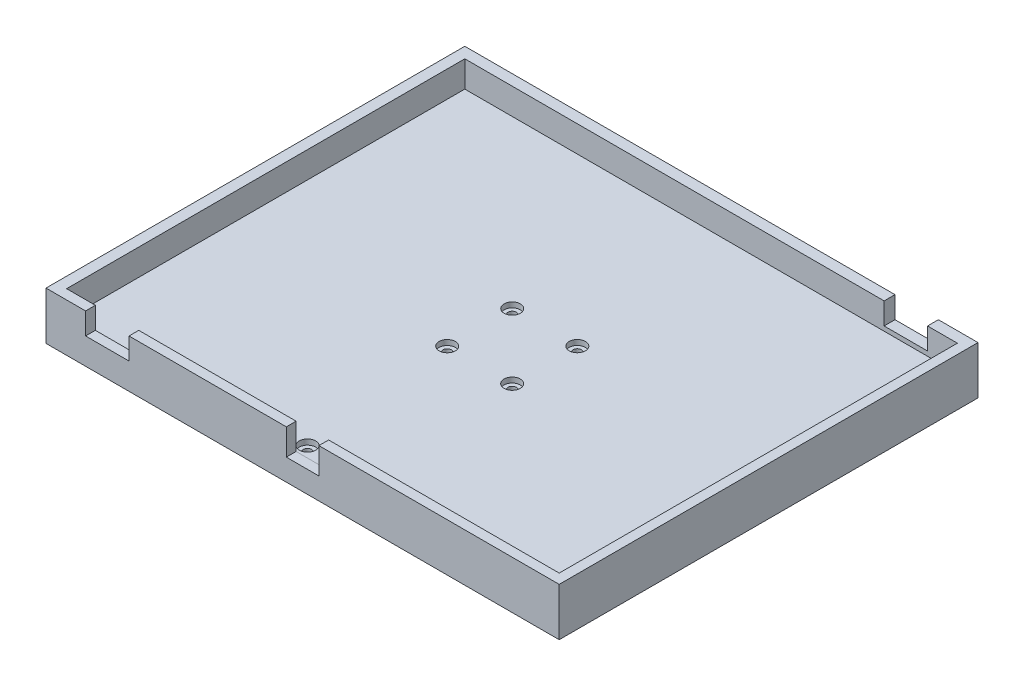
SolidWorks part; units mm, degrees
note: The reader was unsure of these and kept them because the rebuilt part matched: shared geometry of "Sketch44<4>", "Sketch47<2>".
ref_plane "Front Plane" through (0, 0, 0) normal (0, 0, 1) x (1, 0, 0)
ref_plane "Top Plane" through (0, 0, 0) normal (0, 1, 0) x (1, 0, 0)
ref_plane "Right Plane" through (0, 0, 0) normal (1, 0, 0) x (0, 0, -1)
sketch "Sketch2" plane through (0, 0, 0) normal (0, 1, 0) x (1, 0, 0)
  line L1 (0, 0) -> (227, 0)
  line L2 (0, 0) -> (0, -183.5)
  line L3 (0, -183.5) -> (227, -183.5)
  line L4 (227, 0) -> (227, -183.5)
  line L5 (-5, 5) -> (231.5, 5)
  line L6 (-5, 5) -> (-5, -188)
  line L7 (-5, -188) -> (231.5, -188)
  line L8 (231.5, 5) -> (231.5, -188)
  dimension "D1" = 227
  dimension "D2" = 183.5
  dimension "D3" = 236.5
  dimension "D4" = 5
  dimension "D5" = 193
  dimension "D6" = 5
extrude "Boss-Extrude1" add sketch "Sketch2" along normal blind 12.1
sketch "Sketch3" plane through (0, 0, 0) normal (0, -1, 0) x (1, 0, 0)
  line L1 (-5, 188) -> (231.5, 188)
  line L2 (-5, 188) -> (-5, -5)
  line L3 (-5, -5) -> (231.5, -5)
  line L4 (231.5, 188) -> (231.5, -5)
extrude "Boss-Extrude2" add sketch "Sketch3" along normal blind 10
sketch "Sketch4" plane through (-5, 0, 0) normal (-1, 0, 0) x (0, 0, 1)
  line L0 (-5, 12.1) -> (188, 12.1) construction
  line L1 (81.5, 12.1) -> (101.5, 12.1)
  line L2 (81.5, 12.1) -> (81.5, 2.1)
  line L3 (81.5, 2.1) -> (101.5, 2.1)
  line L4 (101.5, 12.1) -> (101.5, 2.1)
  line L5 (91.5, -10) -> (91.5, 12.1)
  line L6 (188, -10) -> (-5, -10) construction
  line M4 (188, 12.1) -> (-5, 12.1)
  dimension "D1" = 10
  dimension "D2" = 20
  dimension "D3" = 10
extrude "Cut-Extrude1" cut sketch "Sketch4" against normal blind 5 contours L5 L3 L4 M4 | L3 L5 L1 L2
sketch "Sketch7" plane through (0, 0, 188) normal (0, 0, 1) x (1, 0, 0)
  line L0 (113.25, 12.1) -> (113.25, -10) construction
  line L1 (-5, 12.1) -> (231.5, 12.1) construction
  line L2 (231.5, -10) -> (-5, -10) construction
  line L4 (13.25, 12.1) -> (33.25, 12.1)
  line L5 (13.25, 12.1) -> (13.25, 2.1)
  line L6 (13.25, 2.1) -> (33.25, 2.1)
  line L7 (33.25, 12.1) -> (33.25, 2.1)
  dimension "D1" = 20
  dimension "D2" = 100
  dimension "D3" = 10
extrude "Cut-Extrude2" cut sketch "Sketch7" against normal blind 5
sketch "Sketch8" plane through (0, 0, -5) normal (0, 0, -1) x (-1, 0, 0)
  line L0 (-113.25, 12.1) -> (-113.25, -10) construction
  line L1 (-231.5, 12.1) -> (5, 12.1) construction
  line L2 (5, -10) -> (-231.5, -10) construction
  line L4 (-213.25, 12.1) -> (-193.25, 12.1)
  line L5 (-213.25, 12.1) -> (-213.25, 2.1)
  line L6 (-213.25, 2.1) -> (-193.25, 2.1)
  line L7 (-193.25, 12.1) -> (-193.25, 2.1)
  dimension "D1" = 10
  dimension "20" = 20
  dimension "D2" = 200
extrude "Cut-Extrude3" cut sketch "Sketch8" against normal blind 5
sketch "Sketch11" plane through (0, 0, -5) normal (0, 0, -1) x (-1, 0, 0)
  line L0 (-202.0531, 2.1) -> (-202.0531, -10)
  line L1 (-213.25, 2.1) -> (-193.25, 2.1) construction
  line L2 (5, -10) -> (-231.5, -10) construction
sketch "Sketch21" plane through (0, -10, 0) normal (0, -1, 0) x (1, 0, 0)
  circle A1 centre (128.25, 106.5) radius 1.925
  circle A4 centre (128.25, 76.5) radius 1.925
  circle A5 centre (98.25, 76.5) radius 1.925
  circle A6 centre (98.25, 106.5) radius 1.925
  point P4 (124.8714, 82.0162)
sketch "Sketch32" plane through (0, 0, 0) normal (1, 0, 0) x (0, 0, -1)
  line L0 (0, 0) -> (-183.5, 0) construction
  line L1 (-101.5, 12.1) -> (-81.5, 12.1)
  line L2 (-101.5, 12.1) -> (-101.5, 0)
  line L3 (-101.5, 0) -> (-81.5, 0)
  line L4 (-81.5, 12.1) -> (-81.5, 0)
extrude "Cut-Extrude14" cut sketch "Sketch32" against normal through all
sketch "Sketch34" plane through (0, 0, 0) normal (0, 1, 0) x (1, 0, 0)
  line L0 (113.3485, -91.6275) -> (113.5, -91.75)
  line L3 (113.6511, -91.6279) -> (113.5, -91.75)
  line L5 (-5, -91.5) -> (227, -91.75)
  line L6 (-5, -101.5) -> (-5, -81.5) construction
  line L7 (227, -183.5) -> (227, 0) construction
  line L8 (113.5, 0) -> (113.5, -183.5)
  line L9 (227, 0) -> (0, 0) construction
  line L10 (0, -183.5) -> (227, -183.5) construction
  circle A0 centre (128.5, -76.6438) radius 1.925
  circle A1 centre (128.4677, -106.6438) radius 1.925
  circle A2 centre (98.5323, -106.6438) radius 1.925
  circle A3 centre (98.5, -76.6438) radius 1.925
  dimension "D1" = 3.85
  dimension "D2" = 15
  dimension "D3" = 15
extrude "Cut-Extrude16" cut sketch "Sketch34" against normal through all contours A0 | A3 | A2 | A1
sketch "Sketch35" plane through (0, 0, 0) normal (0, 1, 0) x (1, 0, 0)
  line L0 (227, -91.75) -> (-5, -91.5)
  line L1 (227, -183.5) -> (227, 0) construction
  line L2 (-5, -101.5) -> (-5, -81.5) construction
  line L3 (113.5, 0) -> (113.5, -183.5)
  line L4 (227, 0) -> (0, 0) construction
  line L5 (0, -183.5) -> (227, -183.5) construction
  circle A0 centre (128.5, -76.6438) radius 3.75
  circle A1 centre (128.4677, -106.6438) radius 3.75
  circle A2 centre (98.5323, -106.6438) radius 3.75
  circle A3 centre (98.5, -76.6438) radius 3.75
  circle M5 centre (98.5323, -106.6438) radius 1.925
  circle M6 centre (128.5, -76.6438) radius 1.925
  circle M15 centre (98.5, -76.6438) radius 1.925
  dimension "D1" = 7.5
extrude "Cut-Extrude17" cut sketch "Sketch35" against normal blind 2.4 contours A3 M15 | A0 M6 | A2 M5 | A1
sketch "Sketch36" plane through (0, 0, 0) normal (1, 0, 0) x (0, 0, -1)
  line L0 (-81.5, 12.1) -> (-81.5, 0) construction
  line L1 (-101.5, 12.1) -> (-81.5, 12.1)
  line L2 (-101.5, 12.1) -> (-101.5, 0)
  line L3 (-101.5, 0) -> (-81.5, 0)
  line L4 (-81.5, 12.1) -> (-81.5, 0)
extrude "Boss-Extrude9" add sketch "Sketch36" along direction (1, 0, 0) on the side against the normal up to vertex (5 mm away)
sketch "Sketch37" plane through (0, 0, 188) normal (0, 0, 1) x (1, 0, 0)
  line L0 (113.25, -10) -> (113.25, 12.1)
  line L1 (231.5, -10) -> (-5, -10) construction
  line L2 (33.25, 12.1) -> (231.5, 12.1) construction
  line L4 (105.75, 12.1001) -> (120.75, 12.1001)
  line L5 (105.75, 12.1001) -> (105.75, 0.0001)
  line L6 (105.75, 0.0001) -> (120.75, 0.0001)
  line L7 (120.75, 12.1001) -> (120.75, 0.0001)
  line M11 (231.5, 12.1) -> (33.25, 12.1)
  dimension "D1" = 12.1
  dimension "D2" = 15
  dimension "0" = 0.0001
  dimension "D3" = 7.5
extrude "Cut-Extrude18" cut sketch "Sketch37" against normal blind 5 contours L5 L6 L0 M11 | L7 L0 L6 M11
sketch "Sketch41" plane through (0, 0, 0) normal (0, 1, 0) x (1, 0, 0)
  line L0 (113.5, 0) -> (113.5, -147.1209)
  line L1 (227, 0) -> (0, 0) construction
  line L2 (227, -91.75) -> (45.6317, -91.75)
  line L3 (227, -183.5) -> (227, 0) construction
  circle A0 centre (128.5, -76.6438) radius 1.925 construction
  circle A2 centre (128.5, -76.6438) radius 3.75 construction
  dimension "D2" = 15.1062
  dimension "D3" = 15.1062
  dimension "D1" = 15
sketch "Sketch44" plane through (0, 0, 0) normal (0, 1, 0) x (1, 0, 0)
  line L0 (113.5, 0) -> (113.5, -183.5) construction
  line L1 (227, 0) -> (0, 0) construction
  line L2 (0, -183.5) -> (227, -183.5) construction
  line L3 (0, -91.75) -> (227, -91.75) construction
  line L4 (0, 0) -> (0, -183.5) construction
  line L5 (227, -183.5) -> (227, 0) construction
  line L6 (120.75, -183.5) -> (227, -183.5) construction
  circle A2 centre (121, -178.5) radius 1.925
  circle A4 centre (106, -178.5) radius 1.925
  circle A5 centre (121, -178.5) radius 3.75
  circle A6 centre (106, -178.5) radius 3.75
  point P18 (106, -176.3522)
  dimension "D1" = 3.85
  dimension "D2" = 7.5
  dimension "D3" = 7.5
  dimension "D4" = 7.5
  dimension "D5" = 5
extrude "Cut-Extrude21" cut sketch "Sketch44" against normal through all both and the other way through all contours A4 | A2 | A6
extrude "Cut-Extrude22" cut sketch "Sketch44<4>" against normal blind 2.5 contours A6
sketch "Sketch44<4>" plane through (0, 0, 0) normal (0, 1, 0) x (1, 0, 0) same geometry as "Sketch44"
sketch "Sketch47" plane through (0, 0, 0) normal (0, 1, 0) x (1, 0, 0)
  line L0 (227, -91.75) -> (0, -91.75) construction
  line L1 (227, -183.5) -> (227, 0) construction
  line L2 (0, 0) -> (0, -183.5) construction
  circle A0 centre (222, -84.25) radius 1.925
  circle A1 centre (222, -84.25) radius 3.75
  circle A2 centre (222, -99.25) radius 3.75
  circle A3 centre (222, -99.25) radius 1.925
  dimension "D1" = 3.85
  dimension "D2" = 7.5
  dimension "D3" = 5
  dimension "D4" = 7.5
extrude "Cut-Extrude23" cut sketch "Sketch47" against normal blind 2.5
extrude "Cut-Extrude24" cut sketch "Sketch47<2>" against normal through all contours A0 | A3
sketch "Sketch47<2>" plane through (0, 0, 0) normal (0, 1, 0) x (1, 0, 0) same geometry as "Sketch47"
